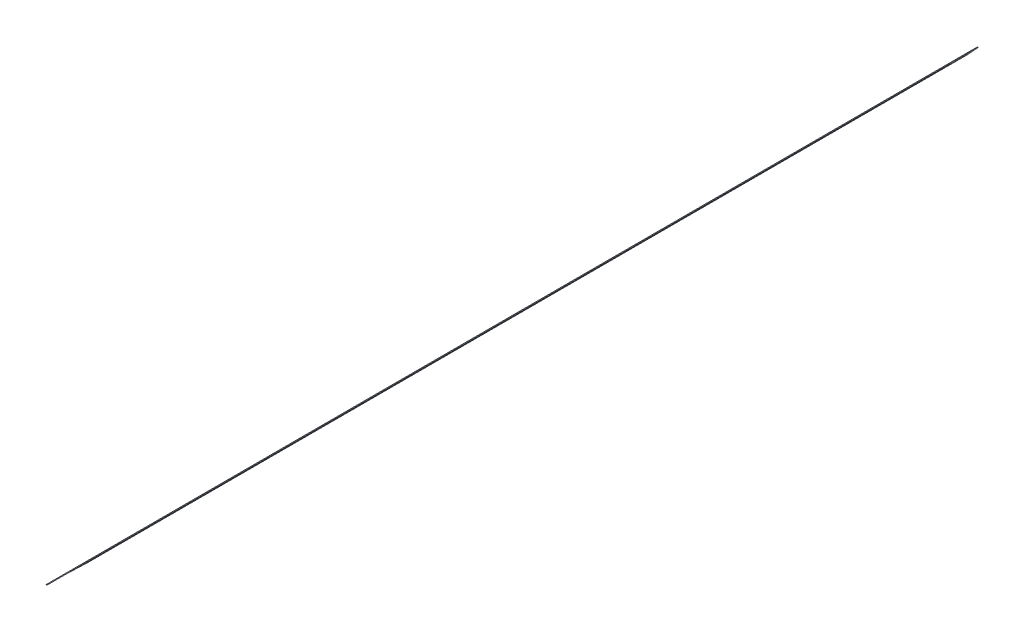
SolidWorks part; units mm, degrees
material "Tape Measure"
ref_plane "Front Plane" through (0, 0, 0) normal (0, 0, 1) x (1, 0, 0)
ref_plane "Top Plane" through (0, 0, 0) normal (0, 1, 0) x (1, 0, 0)
ref_plane "Right Plane" through (0, 0, 0) normal (1, 0, 0) x (0, 0, -1)
sketch "Sketch1" plane through (0, 0, 0) normal (0, 0, 1) x (1, 0, 0)
  line L0 (0.099, 0) -> (-0.099, 0)
  line L1 (0.099, 0) -> (4.2426, 4.1436)
  line L4 (4.2426, 4.1436) -> (4.1436, 4.2426)
  line L5 (4.1436, 4.2426) -> (-0.099, 0)
  point P4 (0, 0)
  dimension "D1" = 45
  dimension "D2" = 0.14
  dimension "D3" = 6
extrude "Boss-Extrude1" add sketch "Sketch1" along normal blind 6.5
sketch "Sketch2" plane through (4.1931, 4.1931, 0) normal (0.7071, 0.7071, 0) x (0, 0, -1)
  line L4 (0, -0.07) -> (0, 0.07)
  line L5 (0, 0.07) -> (-6.5, 0.07)
  line L6 (-6.5, 0.07) -> (-6.5, -0.07)
  line L7 (-6.5, -0.07) -> (0, -0.07)
  line L8 (0, -0.07) -> (0, 0.07)
  line L9 (0, 0.07) -> (-6.5, 0.07)
  line L10 (-6.5, 0.07) -> (-6.5, -0.07)
  line L11 (-6.5, -0.07) -> (0, -0.07)
  dimension "D1" = 0
ref_plane "Plane1" through (6.3145, 6.3145, 0) normal (0.7071, 0.7071, 0) x (0, 0, -1)
sketch "Sketch3" plane through (6.3145, 6.3145, 0) normal (0.7071, 0.7071, 0) x (0, 0, -1)
  line L0 (-6.5, 0.07) -> (-6.5, -0.0705)
  line L1 (0, 0.07) -> (0, -0.0705)
  line L4 (0, -0.07) -> (0, 0.07)
  line L5 (0, 0.07) -> (-6.5, 0.07)
  line L6 (-6.5, 0.07) -> (-6.5, -0.07)
  line L7 (-6.5, -0.07) -> (0, -0.07)
  line L8 (0, -0.07) -> (0, 0.07) construction
  line L9 (0, 0.07) -> (-6.5, 0.07) construction
  line L10 (-6.5, 0.07) -> (-6.5, -0.07) construction
  line L11 (-6.5, -0.07) -> (0, -0.07) construction
  arc A0 (-6.5, 0.07) -> (0, 0.07) centre (-3.25, 37.7232) ccw
  arc A1 (-6.5, -0.0705) -> (0, -0.0705) centre (-3.25, 37.7232) ccw
  arc A2 (-6.512, -0.0695) -> (0.012, -0.0695) centre (-3.25, 37.7232) ccw construction
  dimension "D1" = 0
  dimension "D2" = 0.14
loft "Loft1" add profiles "Sketch2", "Sketch3" connector at (4.1436, 4.2426, 6.5) connector at (6.265, 6.364, 6.5)
sketch "Sketch4" [suppressed] plane through (6.3145, 6.3145, 0) normal (0.7071, 0.7071, 0) x (0, 0, -1)
  line L2 (-6.5, 0.07) -> (-6.5, -0.0705)
  line L3 (0, -0.0705) -> (0, 0.07)
  line L4 (-6.5, 0.07) -> (-6.5, -0.0705)
  line L5 (0, -0.0705) -> (0, 0.07)
  arc A2 (-6.5, 0.07) -> (0, 0.07) centre (-3.25, 37.7232) ccw
  arc A3 (-6.5, -0.0705) -> (0, -0.0705) centre (-3.25, 37.7232) ccw
  arc A4 (-6.5, 0.07) -> (0, 0.07) centre (-3.25, 37.7232) ccw
  arc A5 (-6.5, -0.0705) -> (0, -0.0705) centre (-3.25, 37.7232) ccw
  dimension "D1" = 0
extrude "Boss-Extrude2" [suppressed] add sketch "Sketch4" along normal blind 62
sketch "Sketch5" [suppressed] plane through (6.3145, 6.3145, 0) normal (0.7071, 0.7071, 0) x (0, 0, -1)
  line L2 (-6.5, 0.07) -> (-6.5, -0.0705)
  line L3 (0, -0.0705) -> (0, 0.07)
  line L4 (-6.5, 0.07) -> (-6.5, -0.0705)
  line L5 (0, -0.0705) -> (0, 0.07)
  arc A2 (-6.5, 0.07) -> (0, 0.07) centre (-3.25, 37.7232) ccw
  arc A3 (-6.5, -0.0705) -> (0, -0.0705) centre (-3.25, 37.7232) ccw
  arc A4 (-6.5, 0.07) -> (0, 0.07) centre (-3.25, 37.7232) ccw
  arc A5 (-6.5, -0.0705) -> (0, -0.0705) centre (-3.25, 37.7232) ccw
  dimension "D1" = 0
extrude "Boss-Extrude3" [suppressed] add sketch "Sketch5" along normal blind 28
sketch "Sketch6" plane through (6.3145, 6.3145, 0) normal (0.7071, 0.7071, 0) x (0, 0, -1)
  line L2 (-6.5, 0.07) -> (-6.5, -0.0705)
  line L3 (0, -0.0705) -> (0, 0.07)
  line L4 (-6.5, 0.07) -> (-6.5, -0.0705)
  line L5 (0, -0.0705) -> (0, 0.07)
  arc A2 (-6.5, 0.07) -> (0, 0.07) centre (-3.25, 37.7232) ccw
  arc A3 (-6.5, -0.0705) -> (0, -0.0705) centre (-3.25, 37.7232) ccw
  arc A4 (-6.5, 0.07) -> (0, 0.07) centre (-3.25, 37.7232) ccw
  arc A5 (-6.5, -0.0705) -> (0, -0.0705) centre (-3.25, 37.7232) ccw
  dimension "D1" = 0
extrude "Boss-Extrude4" add sketch "Sketch6" along normal blind 254
sketch "Sketch7" [suppressed] plane through (0, 0, 0) normal (0, 0, 1) x (1, 0, 0)
  line L8 (4.1436, 4.2426) -> (4.2426, 4.1436)
  line L10 (-6.0003, 12.75) -> (0.6198, 12.75)
  line L11 (4.1436, 4.2426) -> (-0.099, 0) construction
  line L12 (-6.0003, 12.75) -> (-6.0003, 12.89)
  line L13 (-6.0003, 12.89) -> (0.6198, 12.89)
  circle A0 centre (-6.0003, 7.75) radius 5 construction
  circle A1 centre (-6.0003, 7.75) radius 5 construction
  arc A4 (4.1436, 4.2426) -> (0.6198, 12.75) centre (0.6198, 7.7665) ccw
  arc A5 (4.2426, 4.1436) -> (0.6198, 12.89) centre (0.6198, 7.7665) ccw
  arc A6 (4.2426, 4.1436) -> (0.6198, 12.89) centre (0.6198, 7.7665) ccw construction
  arc A7 (4.1436, 4.2426) -> (0.6198, 12.75) centre (0.6198, 7.7665) ccw construction
sketch "Sketch8" [suppressed] plane through (0, 0, 0) normal (0, 0, 1) x (1, 0, 0)
  line L6 (-6.0003, 12.89) -> (0.6198, 12.89)
  line L8 (-6.0003, 12.75) -> (0.6198, 12.75)
  line L9 (-6.0003, 12.89) -> (-6.0003, 12.75)
  line L10 (0.099, 0) -> (4.2426, 4.1436) construction
  line L11 (4.1436, 4.2426) -> (4.2426, 4.1436)
  line L15 (4.1436, 4.2426) -> (-0.099, 0)
  line L16 (-0.099, 0) -> (0.099, 0)
  line L17 (0.099, 0) -> (4.2426, 4.1436)
  line L18 (4.2426, 4.1436) -> (4.1436, 4.2426)
  line L19 (4.1436, 4.2426) -> (-0.099, 0) construction
  line L20 (-0.099, 0) -> (0.099, 0) construction
  line L21 (0.099, 0) -> (4.2426, 4.1436) construction
  circle A0 centre (-6.0003, 7.75) radius 5 construction
  circle A1 centre (-6.0003, 7.75) radius 5 construction
  arc A4 (4.1436, 4.2426) -> (0.6198, 12.75) centre (0.6198, 7.7665) ccw
  arc A5 (4.2426, 4.1436) -> (0.6198, 12.89) centre (0.6198, 7.7665) ccw
  arc A6 (2.8966, 3.1767) -> (0.6198, 12.89) centre (0.6198, 7.7665) ccw construction
  arc A7 (2.8344, 3.3021) -> (0.6198, 12.75) centre (0.6198, 7.7665) ccw construction
  dimension "D1" = 0
sketch "Sketch9" [suppressed] plane through (0, 0, 0) normal (0, 0, 1) x (1, 0, 0)
  line L4 (-6.0003, 12.75) -> (0.6198, 12.75)
  line L5 (4.1436, 4.2426) -> (-0.099, 0) construction
  line L6 (0.6198, 12.89) -> (-6.0003, 12.89)
  line L7 (-6.0003, 12.89) -> (-6.0003, 12.75)
  line L8 (4.1436, 4.2426) -> (4.2426, 4.1436)
  line L12 (4.1436, 4.2426) -> (-0.099, 0)
  line L13 (-0.099, 0) -> (0.099, 0)
  line L14 (0.099, 0) -> (4.2426, 4.1436)
  line L15 (4.2426, 4.1436) -> (4.1436, 4.2426)
  line L16 (4.1436, 4.2426) -> (-0.099, 0) construction
  line L17 (-0.099, 0) -> (0.099, 0) construction
  line L18 (0.099, 0) -> (4.2426, 4.1436) construction
  circle A0 centre (-6.0003, 7.75) radius 5 construction
  circle A1 centre (-6.0003, 7.75) radius 5 construction
  arc A2 (4.1436, 4.2426) -> (0.6198, 12.75) centre (0.6198, 7.7665) ccw
  arc A3 (4.2426, 4.1436) -> (0.6198, 12.89) centre (0.6198, 7.7665) ccw
  arc A4 (4.3651, 4.2704) -> (0.6198, 12.89) centre (0.6198, 7.7665) ccw construction
  arc A5 (4.2628, 4.3659) -> (0.6198, 12.75) centre (0.6198, 7.7665) ccw construction
  dimension "D1" = 0
sketch "Sketch12" [suppressed] plane through (0, 0, 0) normal (0, 0, 1) x (1, 0, 0)
  circle A0 centre (-6.0003, 7.75) radius 5 construction
  circle A1 centre (-6.0003, 7.75) radius 5
curve "Helix/Spiral1" [suppressed]
sketch "Sketch13" [suppressed] plane through (0, 0, 0) normal (0, 0, 1) x (1, 0, 0)
  line L4 (-6.0009, 12.89) -> (-6.0003, 12.89)
  line L5 (-6.0003, 12.89) -> (-6.0003, 12.75)
  line L6 (-9.9944, 4.8472) -> (-9.8815, 4.9301)
  spline S1 degree 3 poles (-1864.3601, -716.2327) (77.7894, -123.417) (14.4336, 18.5831) (-7.7338, 12.4516) (-8.143, 12.2774) (-8.9013, 11.8281) (-9.2502, 11.5531) (-9.8634, 10.9216) (-10.1277, 10.5653) (-10.5536, 9.7962) (-10.7151, 9.3836) (-10.9244, 8.5309) (-10.9721, 8.0909) (-10.9506, 7.2143) (-10.8815, 6.7777) (-10.6315, 5.9384) (-10.4506, 5.5357) (-9.99, 4.7922) (-9.7103, 4.4514) (-9.0719, 3.8553) (-8.7131, 3.6) (-7.9417, 3.1924) (-7.5292, 3.0402) (-6.6791, 2.8493) (-6.2416, 2.8105) (-5.3723, 2.8489) (-4.9405, 2.926) (-4.1127, 3.1905) (-3.7167, 3.3778) (-2.988, 3.8493) (-2.6553, 4.1334) (-2.0764, 4.7785) (-1.8301, 5.1394) (-1.4408, 5.9126) (-1.2979, 6.3249) (-1.125, 7.172) (-1.0951, 7.6068) (-1.1777, 8.8993) (-1.4662, 9.7438) (-2.4301, 11.1713) (-3.1043, 11.7524) (-4.6537, 12.4945) (-5.5269, 12.6546) (-7.2344, 12.5118) (-8.0665, 12.2091) (-9.4638, 11.225) (-10.0271, 10.5449) (-10.7331, 8.9934) (-10.8748, 8.124) (-8.4934, -14.8836) (151.1126, -19.1762) (-319.4999, 1977.1396) knots -1.566439 -1.566439 -1.566439 -1.566439 0.03125 0.03125 0.0625 0.0625 0.09375 0.09375 0.125 0.125 0.15625 0.15625 0.1875 0.1875 0.21875 0.21875 0.25 0.25 0.28125 0.28125 0.3125 0.3125 0.34375 0.34375 0.375 0.375 0.40625 0.40625 0.4375 0.4375 0.46875 0.46875 0.5 0.5 0.53125 0.53125 0.5625 0.5625 0.625 0.625 0.6875 0.6875 0.75 0.75 0.8125 0.8125 0.875 0.875 0.9375 0.9375 2.575705 2.575705 2.575705 2.575705 only from (-6.0003, 12.75) to (-9.8815, 4.9301) construction
  spline S2 degree 3 poles (-6.0003, 12.75) (-6.4421, 12.7479) (-6.8832, 12.6869) (-7.7338, 12.4516) (-8.143, 12.2774) (-8.9013, 11.8281) (-9.2502, 11.5531) (-9.8634, 10.9216) (-10.1277, 10.5653) (-10.5536, 9.7962) (-10.7151, 9.3836) (-10.9244, 8.5309) (-10.9721, 8.0909) (-10.9506, 7.2143) (-10.8815, 6.7777) (-10.6315, 5.9384) (-10.4506, 5.5357) (-9.99, 4.7922) (-9.7103, 4.4514) (-9.0719, 3.8553) (-8.7131, 3.6) (-7.9417, 3.1924) (-7.5292, 3.0402) (-6.6791, 2.8493) (-6.2416, 2.8105) (-5.3723, 2.8489) (-4.9405, 2.926) (-4.1127, 3.1905) (-3.7167, 3.3778) (-2.988, 3.8493) (-2.6553, 4.1334) (-2.0764, 4.7785) (-1.8301, 5.1394) (-1.4408, 5.9126) (-1.2979, 6.3249) (-1.125, 7.172) (-1.0951, 7.6068) (-1.1777, 8.8993) (-1.4662, 9.7438) (-2.4301, 11.1713) (-3.1043, 11.7524) (-4.6537, 12.4945) (-5.5269, 12.6546) (-7.2344, 12.5118) (-8.0665, 12.2091) (-9.4638, 11.225) (-10.0271, 10.5449) (-10.7331, 8.9934) (-10.8748, 8.124) (-10.6998, 6.433) (-10.3833, 5.6135) (-9.8815, 4.9301) knots 0 0 0 0 0.03125 0.03125 0.0625 0.0625 0.09375 0.09375 0.125 0.125 0.15625 0.15625 0.1875 0.1875 0.21875 0.21875 0.25 0.25 0.28125 0.28125 0.3125 0.3125 0.34375 0.34375 0.375 0.375 0.40625 0.40625 0.4375 0.4375 0.46875 0.46875 0.5 0.5 0.53125 0.53125 0.5625 0.5625 0.625 0.625 0.6875 0.6875 0.75 0.75 0.8125 0.8125 0.875 0.875 0.9375 0.9375 1 1 1 1
  spline S3 degree 1 poles (-6.0009, 12.89) (-9.9944, 4.8472) knots 0 0 1 1 construction
  spline S4 degree 3 poles (-6.0009, 12.89) (-6.8976, 12.8857) (-8.7251, 12.3841) (-10.6769, 10.3663) (-11.3462, 7.642) (-10.5461, 4.9607) (-8.5055, 3.0566) (-5.7889, 2.4473) (-3.1437, 3.2933) (-1.2941, 5.3555) (-0.7425, 8.0631) (-1.6336, 10.6714) (-3.716, 12.4665) (-6.4134, 12.9609) (-8.9843, 12.0261) (-10.724, 9.9237) (-11.1649, 7.2417) (-10.5054, 5.5433) (-9.9944, 4.8472) knots 0 0 0 0 0.0625 0.125 0.1875 0.25 0.3125 0.375 0.4375 0.5 0.5625 0.625 0.6875 0.75 0.8125 0.875 0.9375 1 1 1 1
  dimension "D1" = 0.14
sketch "Sketch15" [suppressed] plane through (0, 0, 0) normal (0, 0, 1) x (1, 0, 0)
  circle A0 centre (-6.0003, 7.75) radius 5 construction
  circle A1 centre (-6.0003, 7.75) radius 5
curve "Helix/Spiral2" [suppressed]
sketch "Sketch16" [suppressed] plane through (0, 0, 0) normal (0, 0, 1) x (1, 0, 0)
  line L7 (-6.0009, 12.89) -> (-6.0003, 12.89)
  line L8 (-6.0003, 12.89) -> (-6.0003, 12.75)
  line L10 (-9.9028, 7.7491) -> (-9.7628, 7.75)
  spline S4 degree 3 poles (-1809.1857, -843.1376) (96.4501, -113.1349) (12.8349, 21.3715) (-8.5843, 12.0683) (-9.1462, 11.6735) (-10.0688, 10.6952) (-10.429, 10.1121) (-10.8906, 8.8519) (-10.9917, 8.1753) (-10.9195, 6.8378) (-10.7463, 6.1774) (-10.1541, 4.9788) (-9.7355, 4.4412) (-8.721, 3.5746) (-8.1256, 3.246) (-6.8542, 2.85) (-6.1788, 2.7827) (-4.8568, 2.9194) (-4.2108, 3.1233) (-3.0519, 3.7685) (-2.5394, 4.2095) (-1.7301, 5.2571) (-1.4335, 5.8632) (-1.103, 7.1424) (-1.0692, 7.8149) (-1.2691, 9.1183) (-1.5026, 9.7485) (-2.1984, 10.8655) (-2.6604, 11.3518) (-3.7379, 12.1027) (-4.3529, 12.3671) (-5.6366, 12.6323) (-6.3047, 12.633) (-7.5864, 12.3714) (-8.1995, 12.1094) (-9.2724, 11.3655) (-9.7317, 10.884) (-10.4233, 9.7798) (-10.6553, 9.1575) (-10.8555, 7.8727) (-10.8237, 7.2107) (-10.5021, 5.9535) (-10.2125, 5.3588) (-9.4232, 4.332) (-8.9238, 3.9004) (-7.7961, 3.2689) (-7.1682, 3.0694) (-5.8855, 2.9336) (-5.2312, 2.9974) (-4.0012, 3.3773) (-3.4261, 3.6931) (-2.4473, 4.5251) (-2.044, 5.0409) (-1.4734, 6.189) (-1.3062, 6.8207) (-1.2342, 8.0981) (-1.3293, 8.7432) (-1.7655, 9.9433) (-2.1064, 10.4976) (-2.9784, 11.4268) (-3.509, 11.8012) (-4.6742, 12.3106) (-5.3081, 12.4454) (-6.5771, 12.4545) (-7.2115, 12.3289) (-8.3791, 11.8383) (-8.9116, 11.4736) (-9.7896, 10.5646) (-10.1346, 10.0207) (-10.5825, 8.8417) (-10.6851, 8.2071) (-10.6324, 6.9497) (-10.477, 6.3273) (-9.9342, 5.1947) (-9.547, 4.685) (-8.6038, 3.8596) (-8.0482, 3.5443) (-6.8586, 3.1581) (-6.2251, 3.0873) (-4.9822, 3.2009) (-4.3733, 3.385) (-3.2779, 3.9779) (-2.7919, 4.3862) (-2.0203, 5.3606) (-1.735, 5.9262) (-1.4104, 7.1233) (-1.3712, 7.7542) (-1.5442, 8.9797) (-1.7563, 9.5738) (-2.3967, 10.6298) (-2.8248, 11.0913) (-3.8275, 11.8081) (-4.4015, 12.063) (-5.6029, 12.3262) (-6.2296, 12.3343) (-7.435, 12.1033) (-8.013, 11.8644) (-9.0276, 11.1786) (-9.4638, 10.7322) (-10.1248, 9.7044) (-10.3493, 9.1234) (-10.5514, 7.9209) (-10.529, 7.2998) (-10.2415, 6.1175) (-9.9767, 5.5567) (-9.2483, 4.5853) (-8.785, 4.1751) (-7.735, 3.5706) (-7.1487, 3.3765) (-5.9481, 3.235) (-5.3342, 3.2875) (-4.1774, 3.6296) (-3.635, 3.9191) (-2.7086, 4.6878) (-2.325, 5.1665) (-1.7775, 6.2357) (-1.6139, 6.8256) (-1.5322, 8.0213) (-1.6141, 8.6266) (-2.0092, 9.7554) (-2.3223, 10.2783) (-3.1284, 11.1582) (-3.6211, 11.5147) (-4.7063, 12.0046) (-5.2983, 12.1379) (-6.4862, 12.1606) (-7.0815, 12.0501) (-8.1799, 11.6039) (-8.6824, 11.2685) (-9.5142, 10.4275) (-9.8432, 9.9224) (-10.2754, 8.8241) (-10.3785, 8.2315) (-10.3432, 7.0544) (-10.2048, 6.4704) (-9.7096, 5.4048) (-9.3531, 4.9236) (-8.4801, 4.1411) (-7.964, 3.84) (-6.8557, 3.4655) (-6.264, 3.3923) (-5.1005, 3.4846) (-4.5291, 3.6501) (-3.4983, 4.1921) (-3.0394, 4.5685) (-2.3072, 5.4708) (-2.0343, 5.9963) (-1.7176, 7.1116) (-1.6739, 7.7008) (-1.8219, 8.8481) (-2.0135, 9.4056) (-2.6002, 10.3995) (-2.9951, 10.8355) (-3.9239, 11.5163) (-4.4573, 11.7608) (-5.5767, 12.02) (-6.162, 12.0346) (-7.2903, 11.8322) (-7.8328, 11.6155) (-8.788, 10.9864) (-9.2002, 10.5743) (-9.8288, 9.622) (-10.0449, 9.0821) (-10.247, 7.9616) (-10.2329, 7.3816) (-9.9777, 6.2748) (-9.7368, 5.7484) (-9.0677, 4.8337) (-8.6398, 4.4458) (-7.6667, 3.8701) (-7.1219, 3.6825) (-6.0033, 3.5371) (-5.4299, 3.5793) (-4.347, 3.8856) (-3.8379, 4.1497) (-2.9653, 4.8563) (-2.6022, 5.2986) (-2.0798, 6.2896) (-1.9207, 6.8378) (-1.8313, 7.9519) (-1.9009, 8.5171) (-2.2568, 9.5738) (-2.5428, 10.0648) (-3.2845, 10.8938) (-3.7398, 11.2316) (-4.7458, 11.7002) (-5.296, 11.8309) (-6.4027, 11.8653) (-6.9586, 11.7688) (-7.9868, 11.3653) (-8.4586, 11.0584) (-9.2428, 10.2842) (-9.5548, 9.8173) (-9.9696, 8.7992) (-10.0721, 8.2484) (-10.0522, 7.1519) (-9.9298, 6.6066) (-9.4805, 5.6089) (-9.1539, 5.157) (-8.3498, 4.4189) (-7.8727, 4.1329) (-6.8453, 3.7722) (-6.2955, 3.6975) (-5.2116, 3.7706) (-4.6781, 3.9182) (-3.7131, 4.4112) (-3.2819, 4.7563) (-2.5909, 5.5876) (-2.3312, 6.0735) (-2.0243, 7.1074) (-1.9772, 7.6549) (-2.1022, 8.7235) (-2.2742, 9.2441) (-2.8088, 10.1747) (-3.1711, 10.5843) (-4.0271, 11.2275) (-4.5203, 11.4607) (-5.5579, 11.7139) (-6.1017, 11.7339) (-7.1526, 11.5583) (-7.6591, 11.3628) (-8.5535, 10.7888) (-8.9411, 10.4105) (-9.5355, 9.5326) (-9.7422, 9.0335) (-9.9422, 7.995) (-9.9355, 7.4561) (-9.7107, 6.4253) (-9.4927, 5.9339) (-8.8815, 5.0773) (-8.4885, 4.7124) (-7.5914, 4.1672) (-7.0877, 3.9871) (-6.051, 3.8398) (-5.5184, 3.8727) (-4.5101, 4.1451) (-4.0347, 4.3846) (-3.2173, 5.0307) (-2.8756, 5.437) (-2.3801, 6.3506) (-2.2265, 6.8575) (-2.1313, 7.8898) (-2.1897, 8.4148) (-2.5082, 9.3987) (-2.7681, 9.857) (-3.4467, 10.6339) (-3.8651, 10.952) (-4.7925, 11.3974) (-5.3011, 11.5246) (-6.3264, 11.5686) (-6.8427, 11.4853) (-7.7999, 11.1226) (-8.2405, 10.8433) (-8.9755, 10.1346) (-9.2697, 9.7055) (-16.7719, -8.1064) (107.9181, -79.703) (747.1946, 1855.6279) knots -0.255197 -0.255197 -0.255197 -0.255197 0.007813 0.007813 0.015625 0.015625 0.023438 0.023438 0.03125 0.03125 0.039063 0.039063 0.046875 0.046875 0.054688 0.054688 0.0625 0.0625 0.070313 0.070313 0.078125 0.078125 0.085938 0.085938 0.09375 0.09375 0.101563 0.101563 0.109375 0.109375 0.117188 0.117188 0.125 0.125 0.132813 0.132813 0.140625 0.140625 0.148438 0.148438 0.15625 0.15625 0.164062 0.164062 0.171875 0.171875 0.179687 0.179687 0.1875 0.1875 0.195312 0.195312 0.203125 0.203125 0.210937 0.210937 0.21875 0.21875 0.226562 0.226562 0.234375 0.234375 0.242187 0.242187 0.25 0.25 0.257812 0.257812 0.265625 0.265625 0.273437 0.273437 0.28125 0.28125 0.289062 0.289062 0.296875 0.296875 0.304688 0.304688 0.3125 0.3125 0.320312 0.320312 0.328125 0.328125 0.335938 0.335938 0.34375 0.34375 0.351562 0.351562 0.359375 0.359375 0.367188 0.367188 0.375 0.375 0.382813 0.382813 0.390625 0.390625 0.398438 0.398438 0.40625 0.40625 0.414063 0.414063 0.421875 0.421875 0.429687 0.429687 0.4375 0.4375 0.445312 0.445312 0.453125 0.453125 0.460937 0.460937 0.46875 0.46875 0.476562 0.476562 0.484375 0.484375 0.492187 0.492187 0.5 0.5 0.507812 0.507812 0.515625 0.515625 0.523437 0.523437 0.53125 0.53125 0.539062 0.539062 0.546875 0.546875 0.554687 0.554687 0.5625 0.5625 0.570312 0.570312 0.578125 0.578125 0.585937 0.585937 0.59375 0.59375 0.601562 0.601562 0.609375 0.609375 0.617187 0.617187 0.625 0.625 0.632812 0.632812 0.640625 0.640625 0.648437 0.648437 0.65625 0.65625 0.664062 0.664062 0.671875 0.671875 0.679687 0.679687 0.6875 0.6875 0.695312 0.695312 0.703125 0.703125 0.710937 0.710937 0.71875 0.71875 0.726562 0.726562 0.734375 0.734375 0.742187 0.742187 0.75 0.75 0.757812 0.757812 0.765625 0.765625 0.773438 0.773438 0.78125 0.78125 0.789062 0.789062 0.796875 0.796875 0.804688 0.804688 0.8125 0.8125 0.820312 0.820312 0.828125 0.828125 0.835938 0.835938 0.84375 0.84375 0.851562 0.851562 0.859375 0.859375 0.867188 0.867188 0.875 0.875 0.882812 0.882812 0.890625 0.890625 0.898438 0.898438 0.90625 0.90625 0.914062 0.914062 0.921875 0.921875 0.929688 0.929688 0.9375 0.9375 0.945313 0.945313 0.953125 0.953125 0.960938 0.960938 0.96875 0.96875 0.976563 0.976563 0.984375 0.984375 0.992188 0.992188 1.280899 1.280899 1.280899 1.280899 only from (-6.0003, 12.75) to (-9.7628, 7.75) construction
  spline S5 degree 3 poles (-6.0003, 12.75) (-6.6752, 12.7468) (-7.3485, 12.6051) (-8.5843, 12.0683) (-9.1462, 11.6735) (-10.0688, 10.6952) (-10.429, 10.1121) (-10.8906, 8.8519) (-10.9917, 8.1753) (-10.9195, 6.8378) (-10.7463, 6.1774) (-10.1541, 4.9788) (-9.7355, 4.4412) (-8.721, 3.5746) (-8.1256, 3.246) (-6.8542, 2.85) (-6.1788, 2.7827) (-4.8568, 2.9194) (-4.2108, 3.1233) (-3.0519, 3.7685) (-2.5394, 4.2095) (-1.7301, 5.2571) (-1.4335, 5.8632) (-1.103, 7.1424) (-1.0692, 7.8149) (-1.2691, 9.1183) (-1.5026, 9.7485) (-2.1984, 10.8655) (-2.6604, 11.3518) (-3.7379, 12.1027) (-4.3529, 12.3671) (-5.6366, 12.6323) (-6.3047, 12.633) (-7.5864, 12.3714) (-8.1995, 12.1094) (-9.2724, 11.3655) (-9.7317, 10.884) (-10.4233, 9.7798) (-10.6553, 9.1575) (-10.8555, 7.8727) (-10.8237, 7.2107) (-10.5021, 5.9535) (-10.2125, 5.3588) (-9.4232, 4.332) (-8.9238, 3.9004) (-7.7961, 3.2689) (-7.1682, 3.0694) (-5.8855, 2.9336) (-5.2312, 2.9974) (-4.0012, 3.3773) (-3.4261, 3.6931) (-2.4473, 4.5251) (-2.044, 5.0409) (-1.4734, 6.189) (-1.3062, 6.8207) (-1.2342, 8.0981) (-1.3293, 8.7432) (-1.7655, 9.9433) (-2.1064, 10.4976) (-2.9784, 11.4268) (-3.509, 11.8012) (-4.6742, 12.3106) (-5.3081, 12.4454) (-6.5771, 12.4545) (-7.2115, 12.3289) (-8.3791, 11.8383) (-8.9116, 11.4736) (-9.7896, 10.5646) (-10.1346, 10.0207) (-10.5825, 8.8417) (-10.6851, 8.2071) (-10.6324, 6.9497) (-10.477, 6.3273) (-9.9342, 5.1947) (-9.547, 4.685) (-8.6038, 3.8596) (-8.0482, 3.5443) (-6.8586, 3.1581) (-6.2251, 3.0873) (-4.9822, 3.2009) (-4.3733, 3.385) (-3.2779, 3.9779) (-2.7919, 4.3862) (-2.0203, 5.3606) (-1.735, 5.9262) (-1.4104, 7.1233) (-1.3712, 7.7542) (-1.5442, 8.9797) (-1.7563, 9.5738) (-2.3967, 10.6298) (-2.8248, 11.0913) (-3.8275, 11.8081) (-4.4015, 12.063) (-5.6029, 12.3262) (-6.2296, 12.3343) (-7.435, 12.1033) (-8.013, 11.8644) (-9.0276, 11.1786) (-9.4638, 10.7322) (-10.1248, 9.7044) (-10.3493, 9.1234) (-10.5514, 7.9209) (-10.529, 7.2998) (-10.2415, 6.1175) (-9.9767, 5.5567) (-9.2483, 4.5853) (-8.785, 4.1751) (-7.735, 3.5706) (-7.1487, 3.3765) (-5.9481, 3.235) (-5.3342, 3.2875) (-4.1774, 3.6296) (-3.635, 3.9191) (-2.7086, 4.6878) (-2.325, 5.1665) (-1.7775, 6.2357) (-1.6139, 6.8256) (-1.5322, 8.0213) (-1.6141, 8.6266) (-2.0092, 9.7554) (-2.3223, 10.2783) (-3.1284, 11.1582) (-3.6211, 11.5147) (-4.7063, 12.0046) (-5.2983, 12.1379) (-6.4862, 12.1606) (-7.0815, 12.0501) (-8.1799, 11.6039) (-8.6824, 11.2685) (-9.5142, 10.4275) (-9.8432, 9.9224) (-10.2754, 8.8241) (-10.3785, 8.2315) (-10.3432, 7.0544) (-10.2048, 6.4704) (-9.7096, 5.4048) (-9.3531, 4.9236) (-8.4801, 4.1411) (-7.964, 3.84) (-6.8557, 3.4655) (-6.264, 3.3923) (-5.1005, 3.4846) (-4.5291, 3.6501) (-3.4983, 4.1921) (-3.0394, 4.5685) (-2.3072, 5.4708) (-2.0343, 5.9963) (-1.7176, 7.1116) (-1.6739, 7.7008) (-1.8219, 8.8481) (-2.0135, 9.4056) (-2.6002, 10.3995) (-2.9951, 10.8355) (-3.9239, 11.5163) (-4.4573, 11.7608) (-5.5767, 12.02) (-6.162, 12.0346) (-7.2903, 11.8322) (-7.8328, 11.6155) (-8.788, 10.9864) (-9.2002, 10.5743) (-9.8288, 9.622) (-10.0449, 9.0821) (-10.247, 7.9616) (-10.2329, 7.3816) (-9.9777, 6.2748) (-9.7368, 5.7484) (-9.0677, 4.8337) (-8.6398, 4.4458) (-7.6667, 3.8701) (-7.1219, 3.6825) (-6.0033, 3.5371) (-5.4299, 3.5793) (-4.347, 3.8856) (-3.8379, 4.1497) (-2.9653, 4.8563) (-2.6022, 5.2986) (-2.0798, 6.2896) (-1.9207, 6.8378) (-1.8313, 7.9519) (-1.9009, 8.5171) (-2.2568, 9.5738) (-2.5428, 10.0648) (-3.2845, 10.8938) (-3.7398, 11.2316) (-4.7458, 11.7002) (-5.296, 11.8309) (-6.4027, 11.8653) (-6.9586, 11.7688) (-7.9868, 11.3653) (-8.4586, 11.0584) (-9.2428, 10.2842) (-9.5548, 9.8173) (-9.9696, 8.7992) (-10.0721, 8.2484) (-10.0522, 7.1519) (-9.9298, 6.6066) (-9.4805, 5.6089) (-9.1539, 5.157) (-8.3498, 4.4189) (-7.8727, 4.1329) (-6.8453, 3.7722) (-6.2955, 3.6975) (-5.2116, 3.7706) (-4.6781, 3.9182) (-3.7131, 4.4112) (-3.2819, 4.7563) (-2.5909, 5.5876) (-2.3312, 6.0735) (-2.0243, 7.1074) (-1.9772, 7.6549) (-2.1022, 8.7235) (-2.2742, 9.2441) (-2.8088, 10.1747) (-3.1711, 10.5843) (-4.0271, 11.2275) (-4.5203, 11.4607) (-5.5579, 11.7139) (-6.1017, 11.7339) (-7.1526, 11.5583) (-7.6591, 11.3628) (-8.5535, 10.7888) (-8.9411, 10.4105) (-9.5355, 9.5326) (-9.7422, 9.0335) (-9.9422, 7.995) (-9.9355, 7.4561) (-9.7107, 6.4253) (-9.4927, 5.9339) (-8.8815, 5.0773) (-8.4885, 4.7124) (-7.5914, 4.1672) (-7.0877, 3.9871) (-6.051, 3.8398) (-5.5184, 3.8727) (-4.5101, 4.1451) (-4.0347, 4.3846) (-3.2173, 5.0307) (-2.8756, 5.437) (-2.3801, 6.3506) (-2.2265, 6.8575) (-2.1313, 7.8898) (-2.1897, 8.4148) (-2.5082, 9.3987) (-2.7681, 9.857) (-3.4467, 10.6339) (-3.8651, 10.952) (-4.7925, 11.3974) (-5.3011, 11.5246) (-6.3264, 11.5686) (-6.8427, 11.4853) (-7.7999, 11.1226) (-8.2405, 10.8433) (-8.9755, 10.1346) (-9.2697, 9.7055) (-9.665, 8.7669) (-9.766, 8.2579) (-9.7628, 7.75) knots 0 0 0 0 0.007813 0.007813 0.015625 0.015625 0.023438 0.023438 0.03125 0.03125 0.039063 0.039063 0.046875 0.046875 0.054688 0.054688 0.0625 0.0625 0.070313 0.070313 0.078125 0.078125 0.085938 0.085938 0.09375 0.09375 0.101563 0.101563 0.109375 0.109375 0.117188 0.117188 0.125 0.125 0.132813 0.132813 0.140625 0.140625 0.148438 0.148438 0.15625 0.15625 0.164062 0.164062 0.171875 0.171875 0.179687 0.179687 0.1875 0.1875 0.195312 0.195312 0.203125 0.203125 0.210937 0.210937 0.21875 0.21875 0.226562 0.226562 0.234375 0.234375 0.242187 0.242187 0.25 0.25 0.257812 0.257812 0.265625 0.265625 0.273437 0.273437 0.28125 0.28125 0.289062 0.289062 0.296875 0.296875 0.304688 0.304688 0.3125 0.3125 0.320312 0.320312 0.328125 0.328125 0.335938 0.335938 0.34375 0.34375 0.351562 0.351562 0.359375 0.359375 0.367188 0.367188 0.375 0.375 0.382813 0.382813 0.390625 0.390625 0.398438 0.398438 0.40625 0.40625 0.414063 0.414063 0.421875 0.421875 0.429687 0.429687 0.4375 0.4375 0.445312 0.445312 0.453125 0.453125 0.460937 0.460937 0.46875 0.46875 0.476562 0.476562 0.484375 0.484375 0.492187 0.492187 0.5 0.5 0.507812 0.507812 0.515625 0.515625 0.523437 0.523437 0.53125 0.53125 0.539062 0.539062 0.546875 0.546875 0.554687 0.554687 0.5625 0.5625 0.570312 0.570312 0.578125 0.578125 0.585937 0.585937 0.59375 0.59375 0.601562 0.601562 0.609375 0.609375 0.617187 0.617187 0.625 0.625 0.632812 0.632812 0.640625 0.640625 0.648437 0.648437 0.65625 0.65625 0.664062 0.664062 0.671875 0.671875 0.679687 0.679687 0.6875 0.6875 0.695312 0.695312 0.703125 0.703125 0.710937 0.710937 0.71875 0.71875 0.726562 0.726562 0.734375 0.734375 0.742187 0.742187 0.75 0.75 0.757812 0.757812 0.765625 0.765625 0.773438 0.773438 0.78125 0.78125 0.789062 0.789062 0.796875 0.796875 0.804688 0.804688 0.8125 0.8125 0.820312 0.820312 0.828125 0.828125 0.835938 0.835938 0.84375 0.84375 0.851562 0.851562 0.859375 0.859375 0.867188 0.867188 0.875 0.875 0.882812 0.882812 0.890625 0.890625 0.898438 0.898438 0.90625 0.90625 0.914062 0.914062 0.921875 0.921875 0.929688 0.929688 0.9375 0.9375 0.945313 0.945313 0.953125 0.953125 0.960938 0.960938 0.96875 0.96875 0.976563 0.976563 0.984375 0.984375 0.992188 0.992188 1 1 1 1
  spline S6 degree 1 poles (-6.0009, 12.89) (-9.9028, 7.7491) knots 0 0 1 1 construction
  spline S7 degree 3 poles (-6.0009, 12.89) (-6.6894, 12.8867) (-8.0808, 12.5947) (-10.3946, 10.9741) (-11.6846, 7.4664) (-9.6975, 3.4528) (-5.4403, 2.1309) (-1.5614, 4.2942) (-0.458, 8.5788) (-2.7913, 12.3178) (-7.0916, 13.2026) (-10.6836, 10.7079) (-11.351, 6.4029) (-8.7035, 2.9647) (-4.4048, 2.5131) (-1.1266, 5.3042) (-0.8886, 9.586) (-3.814, 12.6984) (-8.0684, 12.7256) (-11.0097, 9.6753) (-10.8294, 5.4587) (-7.6639, 2.6931) (-3.4951, 3.0772) (-0.9094, 6.348) (-1.493, 10.4593) (-4.8593, 12.8615) (-8.9035, 12.083) (-11.1191, 8.6315) (-10.151, 4.6634) (-6.6242, 2.6369) (-2.7411, 3.7891) (-0.9058, 7.3809) (-2.2361, 11.1707) (-5.8826, 12.8134) (-9.571, 11.3113) (-11.0202, 7.6201) (-9.3531, 4.0408) (-5.6274, 2.7855) (-2.1643, 4.6106) (-1.1029, 8.3608) (-3.0785, 11.7007) (-6.8432, 12.569) (-10.0538, 10.4504) (-10.73, 6.681) (-8.4763, 3.6059) (-4.712, 3.12) (-1.7777, 5.5006) (-1.48, 9.2504) (-3.9792, 12.0389) (-7.7051, 12.151) (-10.3433, 9.5417) (-10.2728, 5.8487) (-7.5621, 3.3649) (-3.911, 3.6144) (-1.5851, 6.4177) (-2.0097, 10.0184) (-4.8967, 12.1834) (-8.4387, 11.588) (-10.4402, 8.6263) (-9.6787, 5.1511) (-6.6513, 3.3151) (-3.2505, 4.2375) (-1.5819, 7.3217) (-2.6591, 10.6404) (-5.793, 12.142) (-8.4783, 11.1158) (-9.6961, 9.3325) (-9.9061, 8.273) (-9.9028, 7.7491) knots 0 0 0 0 0.007812 0.015625 0.03125 0.046875 0.0625 0.078125 0.09375 0.109375 0.125 0.140625 0.15625 0.171875 0.1875 0.203125 0.21875 0.234375 0.25 0.265625 0.28125 0.296875 0.3125 0.328125 0.34375 0.359375 0.375 0.390625 0.40625 0.421875 0.4375 0.453125 0.46875 0.484375 0.5 0.515625 0.53125 0.546875 0.5625 0.578125 0.59375 0.609375 0.625 0.640625 0.65625 0.671875 0.6875 0.703125 0.71875 0.734375 0.75 0.765625 0.78125 0.796875 0.8125 0.828125 0.84375 0.859375 0.875 0.890625 0.90625 0.921875 0.9375 0.953125 0.96875 0.984375 0.992188 1 1 1 1
  dimension "D1" = 0.14
extrude "Boss-Extrude13" [suppressed] add sketch "Sketch8" along normal up to surface (6.5 mm away) up to face at (71.2923, 71.2922, 6.5)
sketch "Sketch17" [suppressed] plane through (0, 0, 0) normal (0, 0, 1) x (1, 0, 0)
  line L0 (-2.8273, 3.8858) -> (-2.7384, 3.7776)
  line L1 (-6.0003, 12.89) -> (-6.0003, 12.75)
  line L2 (-6.0003, 7.75) -> (-2.8273, 3.8858) construction
  line L3 (-6.0003, 12.75) -> (0.6198, 12.75) construction
  arc A3 (-6.0003, 12.89) -> (-2.7384, 3.7776) centre (-6.0003, 7.75) ccw
  arc A5 (-6.0003, 12.75) -> (-2.8273, 3.8858) centre (-6.0003, 7.75) ccw
  dimension "D1" = 50.609
extrude "Boss-Extrude14" [suppressed] add sketch "Sketch17" along normal up to surface (6.5 mm away) up to face at (71.2923, 71.2922, 6.5)
extrude "Boss-Extrude15" [suppressed] add sketch "Sketch9" along normal up to surface (6.5 mm away) up to face at (71.2923, 71.2922, 6.5)
extrude "Boss-Extrude16" [suppressed] add sketch "Sketch13" along normal up to surface (6.5 mm away) up to face at (71.2923, 71.2922, 6.5)
extrude "Boss-Extrude17" [suppressed] add sketch "Sketch7" along normal up to surface (6.5 mm away) up to face at (71.2923, 71.2922, 6.5)
extrude "Boss-Extrude18" [suppressed] add sketch "Sketch16" along normal up to surface (6.5 mm away) up to face at (71.2923, 71.2922, 6.5)
